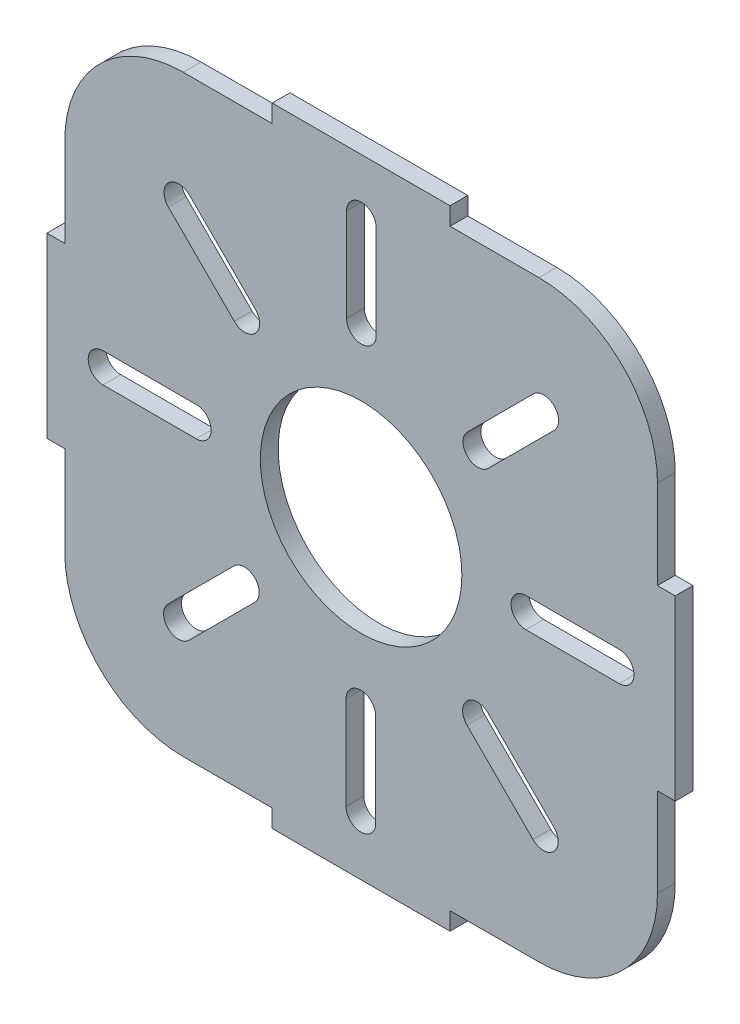
SolidWorks part; units mm, degrees
ref_plane "Plan de face" through (0, 0, 0) normal (0, 0, 1) x (1, 0, 0)
ref_plane "Plan de dessus" through (0, 0, 0) normal (0, 1, 0) x (1, 0, 0)
ref_plane "Plan de droite" through (0, 0, 0) normal (1, 0, 0) x (0, 0, -1)
sketch "Esquisse1" plane through (0, 0, 0) normal (0, 0, 1) x (1, 0, 0)
  line L0 (0, 0) -> (0, 35)
  line L1 (0, 100) -> (35, 100)
  line L2 (100, 100) -> (100, 65)
  line L3 (100, 0) -> (65, 0)
  line L4 (-3, 35) -> (-3, 65)
  line L5 (-3, 65) -> (0, 65)
  line L6 (-3, 35) -> (0, 35)
  line L7 (35, 103) -> (65, 103)
  line L8 (65, 103) -> (65, 100)
  line L9 (35, 103) -> (35, 100)
  line L10 (103, 65) -> (103, 35)
  line L11 (103, 35) -> (100, 35)
  line L12 (103, 65) -> (100, 65)
  line L13 (65, -3) -> (35, -3)
  line L14 (35, -3) -> (35, 0)
  line L15 (65, -3) -> (65, 0)
  line L16 (65, 100) -> (100, 100)
  line L17 (100, 35) -> (100, 0)
  line L18 (35, 0) -> (0, 0)
  line L19 (0, 65) -> (0, 100)
  point P8 (-3, 50)
  point P25 (50, 50)
  dimension "D1" = 100
  dimension "D3" = 3
  dimension "D4" = 30
  dimension "D5" = 4
extrude "Boss.-Extru.1" add sketch "Esquisse1" along normal blind 3
sketch "Esquisse3" plane through (0, 0, 3) normal (0, 0, 1) x (1, 0, 0)
  line L0 (100, 100) -> (0, 0) construction
  line L1 (0, 100) -> (100, 0) construction
sketch "Esquisse2" plane through (0, 0, 3) normal (0, 0, 1) x (1, 0, 0)
  line L0 (100, 100) -> (0, 0) construction
  circle A0 centre (50, 50) radius 17
  dimension "D1" = 34
extrude "Enlèv. mat.-Extru.1" cut sketch "Esquisse2" against normal up to surface (3 mm away) up to face at (50, 50, 0)
fillet "Congé1" radius 20 4 edges at (0, 0, 1.5) (100, 0, 1.5) (100, 100, 1.5) (0, 100, 1.5)
sketch "Esquisse4" plane through (0, 0, 3) normal (0, 0, 1) x (1, 0, 0)
  line L0 (50.0449, 93.5427) -> (50.0449, 77.8009) construction
  line L1 (52.5449, 93.5427) -> (52.5449, 77.8009)
  line L2 (47.5449, 93.5427) -> (47.5449, 77.8009)
  arc A0 (52.5449, 93.5427) -> (47.5449, 93.5427) centre (50.0449, 93.5427) ccw
  arc A1 (47.5449, 77.8009) -> (52.5449, 77.8009) centre (50.0449, 77.8009) ccw
  point P2 (50.0449, 85.6718)
  dimension "D1" = 5
extrude "Enlèv. mat.-Extru.2" cut sketch "Esquisse4" against normal up to next
pattern_circular "Répétition circulaire1" count 8 over 360 about axis through (50, 50, 3) along (0, 0, 1) of "Enlèv. mat.-Extru.2"
